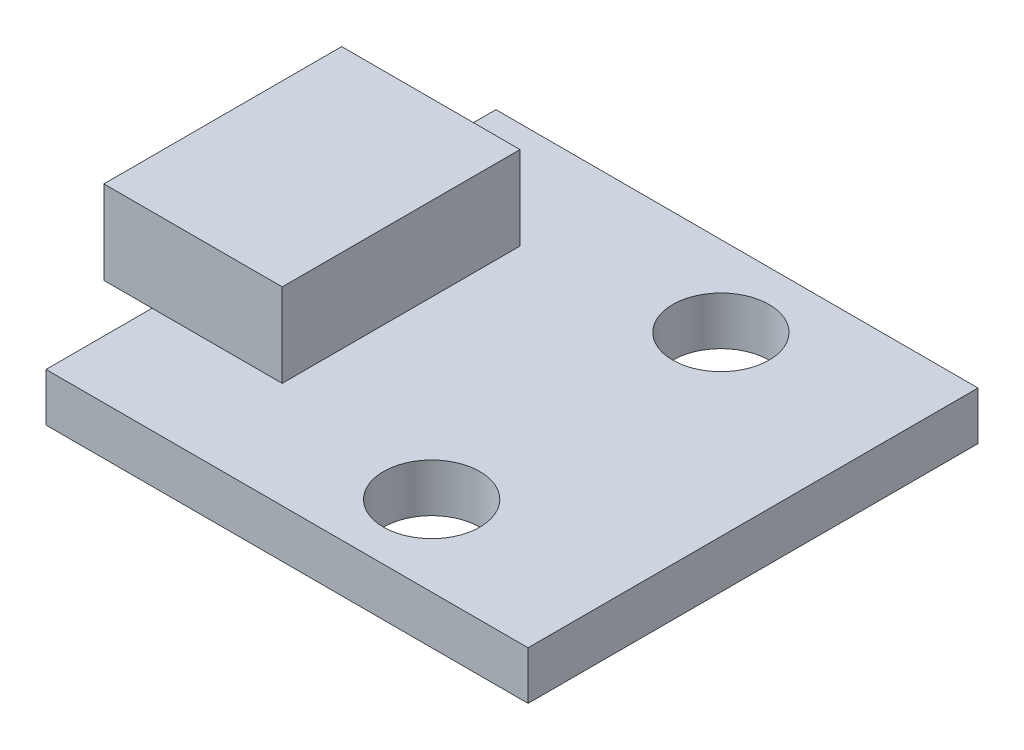
SolidWorks part; units mm, degrees
ref_plane "Спереди" through (0, 0, 0) normal (0, 0, 1) x (1, 0, 0)
ref_plane "Сверху" through (0, 0, 0) normal (0, 1, 0) x (1, 0, 0)
ref_plane "Справа" through (0, 0, 0) normal (1, 0, 0) x (0, 0, -1)
sketch "Эскиз1" plane through (0, 0, 0) normal (0, 1, 0) x (1, 0, 0)
  line L0 (-7.5, 3.7) -> (-7.5, -3.7)
  line L1 (7.5, 7) -> (-7.5, 7)
  line L2 (7.5, 7) -> (7.5, -7)
  line L3 (7.5, -7) -> (-7.5, -7)
  line L4 (-7.5, 7) -> (-7.5, -7)
  line L5 (7.5, 7) -> (-7.5, -7) construction
  line L6 (7.5, -7) -> (-7.5, 7) construction
  line L7 (2, 7) -> (2, -7)
  line L8 (-3.45, 3.7) -> (-9, 3.7)
  line L9 (-3.45, 3.7) -> (-3.45, -3.7)
  line L10 (-3.45, -3.7) -> (-9, -3.7)
  line L11 (-9, 3.7) -> (-9, -3.7)
  line L12 (2, 4.5) -> (2, -4.5)
  line L13 (4.5, -7) -> (4.5, 7)
  circle A0 centre (2, 4.5) radius 1.5
  circle A1 centre (2, -4.5) radius 1.5
  point P0 (0, 0)
  point P9 (-7.5, 0)
  point P18 (2, 0)
  dimension "D8" = 3
  dimension "D9" = 3
  dimension "D1" = 15
  dimension "D2" = 14
  dimension "D3" = 7.4
  dimension "D4" = 5.55
  dimension "D5" = 1.5
  dimension "D6" = 9.5
  dimension "D7" = 9
  dimension "D10" = 3
extrude "Бобышка-Вытянуть1" add sketch "Эскиз1" along normal blind 1.5 contours A1 L7 L3 L13 L1 A0 L12 | L13 L3 L2 L1 | A1 L12 A0 L7 L1 L4 L8 L9 L10 L3 | L10 L9 L8 L0 region at (-5.475, 0, 0) region at (-2.2019, 0, 0) region at (3.4052, 0, 0) region at (6, 0, 0)
extrude "Бобышка-Вытянуть2" add sketch "Эскиз1<3>" along normal blind 2.6 from surface contours L10 L9 L8 L0 | L11 L10 L9 L8 region at (-5.475, 0, 0) starting at face at (0, 1.5, 0)
sketch "Эскиз1<3>" plane through (0, 0, 0) normal (0, 1, 0) x (1, 0, 0) same geometry as "Эскиз1"
